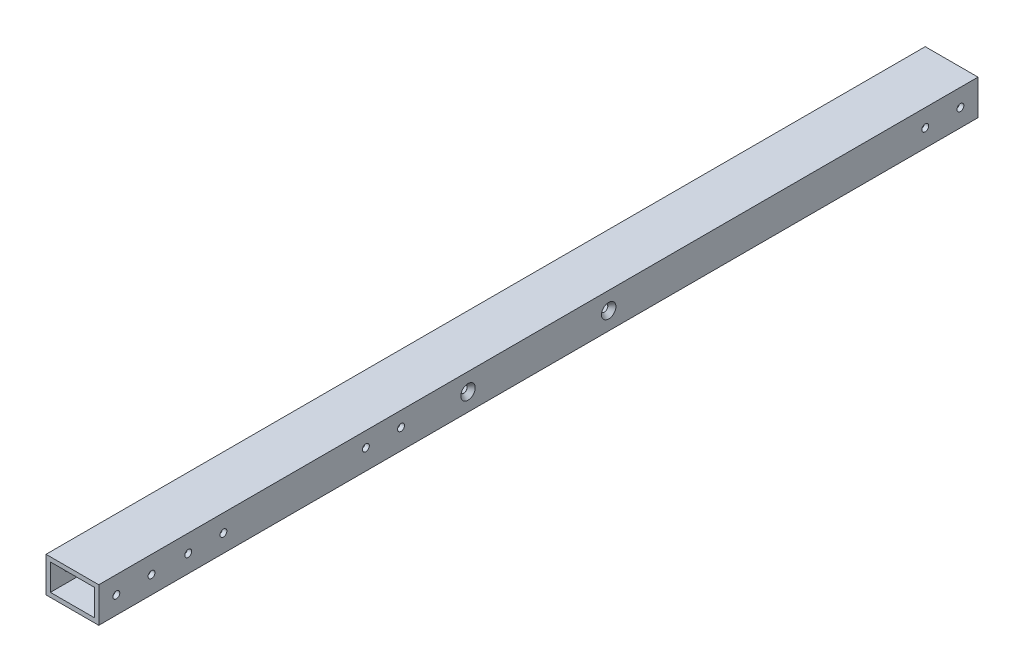
SolidWorks part; units mm, degrees
material "1060 Alloy"
ref_plane "Front Plane" through (0, 0, 0) normal (0, 0, 1) x (1, 0, 0)
ref_plane "Top Plane" through (0, 0, 0) normal (0, 1, 0) x (1, 0, 0)
ref_plane "Right Plane" through (0, 0, 0) normal (1, 0, 0) x (0, 0, -1)
sketch "Sketch1" plane through (0, 0, 0) normal (0, 0, 1) x (1, 0, 0)
  line L0 (-15.875, 9.525) -> (15.875, 9.525)
  line L2 (-19.05, 12.7) -> (19.05, 12.7)
  line L3 (-19.05, 12.7) -> (-19.05, -12.7)
  line L4 (-19.05, -12.7) -> (19.05, -12.7)
  line L5 (19.05, 12.7) -> (19.05, -12.7)
  line L10 (15.875, 9.525) -> (15.875, -9.525)
  line L11 (-15.875, -9.525) -> (15.875, -9.525)
  line L12 (-15.875, 9.525) -> (-15.875, -9.525)
  point P12 (0, 12.7)
  point P14 (19.05, 0)
  dimension "Wall Thickness" = 3.175
  dimension "Outside Width" = 38.1
  dimension "Outside Height" = 25.4
  dimension "Inside Height" = 19.05
  dimension "Inside Width" = 31.75
sketch "Sketch2" plane through (0, 0, 0) normal (1, 0, 0) x (0, 0, -1)
  line L0 (317.5, 0) -> (-317.5, 0)
  point P4 (0, 0)
  point P7 (-317.5, 0)
  point P10 (317.5, 0)
  dimension "Length" = 635
sketch "Sketch3" plane through (0, 0, 0) normal (0, 0, 1) x (1, 0, 0)
  line L21 (19.05, 12.7) -> (-19.05, 12.7)
  line L22 (19.05, -12.7) -> (19.05, 12.7)
  line L23 (-19.05, -12.7) -> (19.05, -12.7)
  line L24 (-19.05, 12.7) -> (-19.05, -12.7)
  line L25 (19.05, 12.7) -> (-19.05, 12.7)
  line L26 (19.05, -12.7) -> (19.05, 12.7)
  line L27 (-19.05, -12.7) -> (19.05, -12.7)
  line L28 (-19.05, 12.7) -> (-19.05, -12.7)
  line L29 (15.875, 9.525) -> (-15.875, 9.525)
  line L30 (15.875, -9.525) -> (15.875, 9.525)
  line L31 (-15.875, -9.525) -> (15.875, -9.525)
  line L32 (-15.875, 9.525) -> (-15.875, -9.525)
  line L33 (15.875, 9.525) -> (-15.875, 9.525)
  line L34 (15.875, -9.525) -> (15.875, 9.525)
  line L35 (-15.875, -9.525) -> (15.875, -9.525)
  line L36 (-15.875, 9.525) -> (-15.875, -9.525)
  dimension "D1" = 0
  dimension "D2" = 0
extrude "Boss-Extrude1" add sketch "Sketch3" along normal up to vertex (317.5 mm away) and the other way up to vertex (317.5 mm away) up to point (0, 0, 317.5) other way up to point (0, 0, -317.5)
sketch "Drawing Reference" plane through (0, 0, 0) normal (1, 0, 0) x (0, 0, -1)
  line L0 (-317.5, 0) -> (317.5, 0) construction
  line L1 (0, -12.7) -> (0, 12.7) construction
  line L2 (-317.5, -12.7) -> (317.5, -12.7) construction
  line L5 (-317.5, 12.7) -> (317.5, 12.7) construction
  point P7 (-290.068, 0)
  point P8 (290.068, 0)
  dimension "D1" = 27.432
sketch "Sketch4" plane through (-19.05, 0, 0) normal (-1, 0, 0) x (0, 0, 1)
  line L0 (-317.5, 0) -> (-304.8, 0)
  line L1 (-317.5, 12.7) -> (-317.5, -12.7) construction
  line L2 (-304.8, 0) -> (-279.4, 0)
  line L3 (317.5, 12.7) -> (317.5, -12.7) construction
  line L4 (317.5, 0) -> (304.8, 0)
  line L5 (304.8, 0) -> (279.4, 0)
  line L6 (0, 0) -> (50.8, 0) construction
  line L7 (0, 0) -> (-50.8, 0) construction
  point P11 (-304.8, 0)
  point P13 (-279.4, 0)
  point P14 (304.8, 0)
  point P15 (279.4, 0)
hole_wizard "#10 Clearance Hole2" positions "Sketch11" profile "Sketch12" hole size "#10" standard "ANSI Inch" end condition through all
sketch "Sketch11" plane through (-19.05, 0, 0) normal (-1, 0, 0) x (0, 0, 1)
  point P0 (-304.8, 0)
  point P3 (-279.4, 0)
  point P6 (279.4, 0)
  point P9 (304.8, 0)
sketch "Sketch12" plane through (-19.05, 0, -304.8) normal (0, 1, 0) x (0, 0, 1)
  line L0 (0, 0) -> (0, 38.1)
  line L1 (0, 38.1) -> (2.4892, 38.1)
  line L2 (2.4892, 38.1) -> (2.4892, 0)
  line L5 (2.4892, 0) -> (0, 0)
  line L11 (0, -6.35) -> (0, 107.95) construction
  dimension "Thru Hole Dia." = 4.9784
  dimension "Thru Hole Depth" = 38.1
hole_wizard "#10 Clearance Hole4" positions "Sketch14" profile "Sketch16" hole size "#10" standard "ANSI Inch" end condition through all
sketch "Sketch14" plane through (19.05, 0, 0) normal (1, 0, 0) x (0, 0, -1)
  point P33 (-252.857, 0)
  point P36 (-227.457, 0)
  point P42 (-124.587, 1.9434)
  point P45 (-99.187, 1.9434)
sketch "Sketch16" plane through (19.05, 0, 252.857) normal (0, 1, 0) x (0, 0, -1)
  line L0 (0, 0) -> (0, 38.1)
  line L1 (0, 38.1) -> (2.4892, 38.1)
  line L2 (2.4892, 38.1) -> (2.4892, 0)
  line L5 (2.4892, 0) -> (0, 0)
  line L11 (0, -6.35) -> (0, 107.95) construction
  dimension "Thru Hole Dia." = 4.9784
  dimension "Thru Hole Depth" = 38.1
hole_wizard "#10 Clearance Hole3" positions "Sketch20" profile "Sketch21" hole size "#10" standard "ANSI Inch" end condition through all
sketch "Sketch20" plane through (-19.05, 0, 0) normal (-1, 0, 0) x (0, 0, 1)
  point P0 (-50.8, 0)
  point P3 (50.8, 0)
sketch "Sketch21" plane through (-19.05, 0, -50.8) normal (0, 1, 0) x (0, 0, 1)
  line L0 (0, 0) -> (0, 38.1)
  line L1 (0, 38.1) -> (5.207, 38.1)
  line L2 (2.4892, 34.9735) -> (2.4892, 0)
  line L5 (2.4892, 0) -> (0, 0)
  line L7 (5.207, 38.1) -> (2.4892, 34.9735)
  line L8 (-5.207, 38.1) -> (-2.4892, 34.9735) construction
  line L11 (0, -6.35) -> (0, 107.95) construction
  dimension "Thru Hole Dia." = 4.9784
  dimension "Thru Hole Depth" = 38.1
  dimension "Far C'Sink Dia." = 10.414
  dimension "Far C'Sink Angle" = 82
equation "\"D1@Drawing Reference\"=\"Outside Width@Sketch1\" * 0.72"
